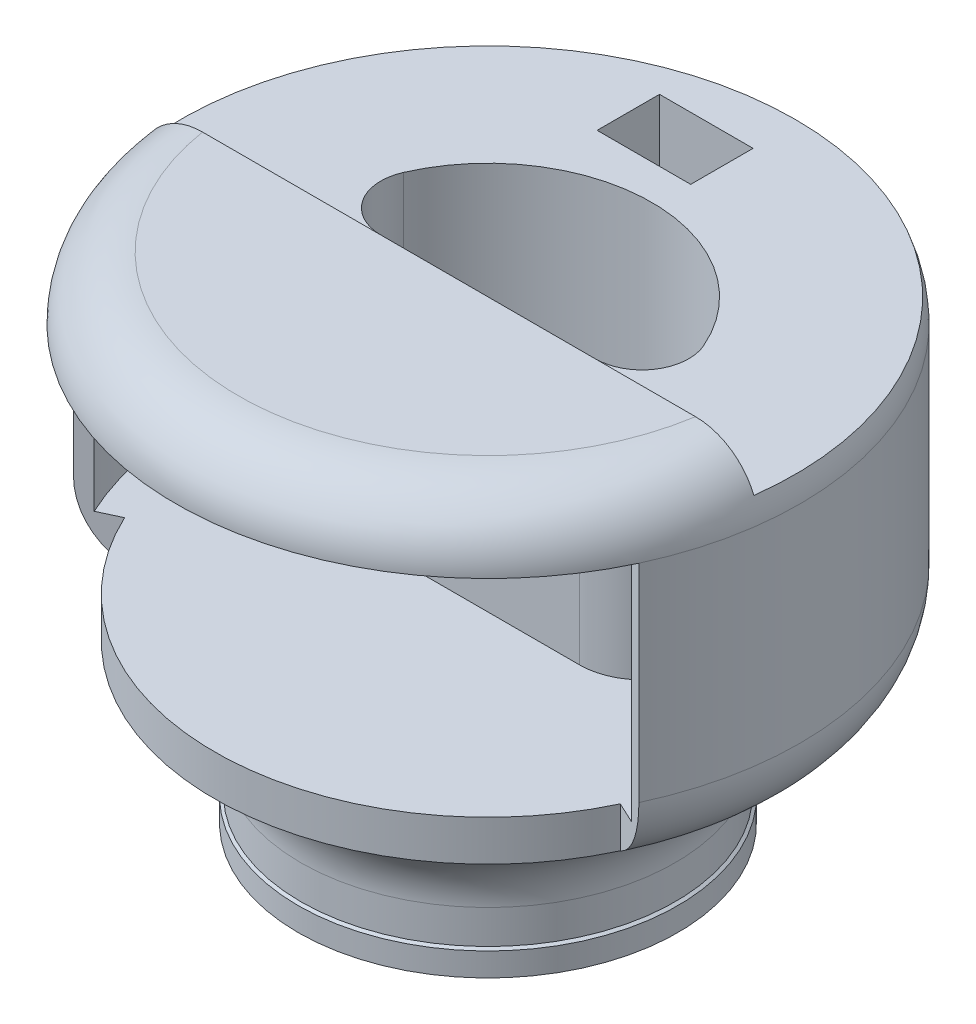
SolidWorks part; units mm, degrees
ref_plane "Front Plane" through (0, 0, 0) normal (0, 0, 1) x (1, 0, 0)
ref_plane "Top Plane" through (0, 0, 0) normal (0, 1, 0) x (1, 0, 0)
ref_plane "Right Plane" through (0, 0, 0) normal (1, 0, 0) x (0, 0, -1)
sketch "Sketch1" plane through (0, 0, 0) normal (0, 0, 1) x (1, 0, 0)
  line L0 (0, 0) -> (0, 90.2242) construction
  line L28 (0, 63.4279) -> (32, 63.4279)
  line L29 (40, 55.4279) -> (40, 28.8468)
  line L30 (22.5, 0) -> (24.35, 0)
  line L31 (24.35, 0) -> (24.35, 3)
  line L32 (24.35, 3) -> (24, 3.25)
  line L33 (24, 3.25) -> (24, 7.5811)
  line L34 (28.5399, 15.9588) -> (35.4601, 20.4691)
  line L35 (0, 13) -> (22, 13)
  line L36 (22.5, 12.5) -> (22.5, 0)
  line L37 (0, 13) -> (0, 63.4279)
  arc A0 (22, 13) -> (22.5, 12.5) centre (22, 12.5) cw
  arc A1 (24, 7.5811) -> (28.5399, 15.9588) centre (34, 7.5811) cw
  arc A2 (35.4601, 20.4691) -> (40, 28.8468) centre (30, 28.8468) ccw
  arc A3 (32, 63.4279) -> (40, 55.4279) centre (32, 55.4279) cw
  point P11 (22.9, 63.4279)
  point P18 (22.5, 13)
  point P21 (24, 13)
  point P24 (40, 23.4279)
  point P27 (40, 63.4279)
  point P28 (28.5604, 23.4279)
  point P31 (22.5, 17)
  dimension "D8" = 9.75
  dimension "D9" = 0.5
  dimension "D4" = 1.85
  dimension "D1" = 22.5
  dimension "D10" = 10
  dimension "D11" = 10
  dimension "D12" = 8
  dimension "D2" = 40
  dimension "D3" = 40
  dimension "D5" = 1.5
  dimension "D6" = 3
  dimension "D7" = 13
revolve "Revolve1" add sketch "Sketch1" angle 360 about L0
ref_plane "Plane1" through (0, 13, 0) normal (0, -1, 0) x (-1, 0, 0)
sketch "Sketch18" plane through (0, 0, 0) normal (0, 0, 1) x (1, 0, 0)
  line L0 (0, 0) -> (0, 101.5813) construction
  line L1 (-24.35, 0) -> (24.35, 0) construction
sketch "Sketch3" plane through (0, 0, 0) normal (0, 0, 1) x (1, 0, 0)
  point P0 (1.2404, 19.1989)
ref_point "Point1"
ref_plane "Plane2" through (0, 0, 22.9) normal (0, 0, 1) x (1, 0, 0)
ref_plane "Plane3" through (0, 0, 40) normal (0, 0, 1) x (1, 0, 0)
ref_plane "Plane4" through (0, 55.4279, 0) normal (0, 1, 0) x (1, 0, 0)
sketch "Sketch9" plane through (0, 55.4279, 0) normal (0, 1, 0) x (1, 0, 0)
  circle A7 centre (0, 0) radius 38
  circle A8 centre (0, 0) radius 40 construction
  circle A9 centre (0, 0) radius 23
  dimension "D1" = 2
  dimension "D2" = 46
ref_plane "Plane5" through (0, 13, 0) normal (0, -1, 0) x (-1, 0, 0)
sketch "Sketch11" plane through (0, 13, 0) normal (0, -1, 0) x (-1, 0, 0)
  line L0 (-21, 0) -> (21, 0)
  arc A1 (-21, 0) -> (21, 0) centre (0, 0) cw
  dimension "D1" = 42
extrude "Cut-Extrude3" cut sketch "Sketch11" against normal blind 60
ref_plane "Plane6" through (0, 0, -40) normal (0, 0, -1) x (-1, 0, 0)
extrude "Cut-Extrude5" cut sketch "Sketch9" against normal blind 30 and the other way blind 2
sketch "Sketch19" plane through (0, 0, 0) normal (1, 0, 0) x (0, 0, -1)
  line L0 (-47.0647, 55.4279) -> (-35.0647, 55.4279)
  line L1 (31.2976, 55.4279) -> (-31.2976, 55.4279) construction
  line L2 (-35.0647, 55.4279) -> (-35.0647, 18.9279)
  line L3 (-35.0647, 18.9279) -> (-47.0647, 18.9279)
  line L4 (-47.0647, 18.9279) -> (-47.0647, 55.4279)
  dimension "D1" = 12
  dimension "D2" = 36.5
revolve "Cut-Revolve2" cut sketch "Sketch19" angle 65 about L0 other way angle 65
ref_plane "Plane7" through (0, 0, 22.5) normal (0, 0, -1) x (-1, 0, 0)
sketch "Sketch21" plane through (0, 0, 22.5) normal (0, 0, -1) x (-1, 0, 0)
  line L0 (0, 0) -> (0, 101.5813) construction
  line L1 (-1.625, 4) -> (1.625, 4)
  line L2 (-1.625, 4) -> (-1.625, 0)
  line L3 (-1.625, 0) -> (1.625, 0)
  line L4 (1.625, 4) -> (1.625, 0)
  line L5 (-1.625, 4) -> (1.625, 0) construction
  line L6 (-1.625, 0) -> (1.625, 4) construction
  line L7 (-22.5, 0) -> (22.5, 0) construction
  point P0 (0, 2)
  dimension "D1" = 4
  dimension "D2" = 3.25
extrude "Boss-Extrude3" add sketch "Sketch21" along normal blind 1.35
pattern_circular "CirPattern1" count 5 over 360 about axis through (0, 0, 0) along (0, -1, 0) of "Boss-Extrude3"
ref_plane "Plane8" through (0, 20.4691, 0) normal (0, 1, 0) x (1, 0, 0)
sketch "Sketch22" plane through (0, 63.4279, 0) normal (0, 1, 0) x (1, 0, 0)
  line L0 (-40, 0) -> (40, 0)
  arc A0 (-40, 0) -> (40, 0) centre (0, 0) cw
  arc A1 (36.2523, -16.9047) -> (-36.2523, -16.9047) centre (0, 0) ccw construction
extrude "Cut-Extrude9" cut sketch "Sketch22" against normal blind 5
sketch "Sketch23" plane through (0, 0, -40) normal (0, 0, -1) x (-1, 0, 0)
  line L0 (0, 0) -> (0, 101.5813) construction
  line L1 (31.2976, 55.4279) -> (-31.2976, 55.4279) construction
  circle A0 centre (0, 42.1379) radius 10.5
  dimension "D1" = 21
  dimension "D2" = 13.29
extrude "Cut-Extrude10" cut sketch "Sketch23" against normal blind 10
sketch "Sketch24" plane through (0, 58.4279, 0) normal (0, 1, 0) x (1, 0, 0)
  line L1 (-14, 36) -> (3, 36)
  line L2 (-14, 36) -> (-14, 24)
  line L3 (-14, 24) -> (3, 24)
  line L4 (3, 36) -> (3, 24)
  line L5 (-14, 36) -> (3, 24) construction
  line L6 (-14, 24) -> (3, 36) construction
  point P0 (0, 30)
  point P8 (0, 0)
  point P9 (0, 0)
  dimension "D1" = 29
  dimension "D2" = 12
  dimension "D3" = 17
extrude "Boss-Extrude4" add sketch "Sketch24" against normal blind 8
sketch "Sketch26" plane through (0, 58.4279, 0) normal (0, 1, 0) x (1, 0, 0)
  line L0 (-14, 35.327) -> (-14, 24) construction
  line L1 (-11.5, 33.4915) -> (0.5, 33.4915)
  line L2 (-11.5, 33.4915) -> (-11.5, 25.4915)
  line L3 (-11.5, 25.4915) -> (0.5, 25.4915)
  line L4 (0.5, 33.4915) -> (0.5, 25.4915)
  line L5 (-11.5, 33.4915) -> (0.5, 25.4915) construction
  line L6 (-11.5, 25.4915) -> (0.5, 33.4915) construction
  arc A0 (39.4162, 0) -> (-39.4162, 0) centre (0, 0) ccw construction
  point P0 (-5.5, 29.4915)
  dimension "D1" = 30
  dimension "D2" = 8
  dimension "D3" = 12
  dimension "D4" = 2.5
extrude "Cut-Extrude11" cut sketch "Sketch26" against normal blind 10
sketch "Sketch27" plane through (3, 0, 0) normal (1, 0, 0) x (0, 0, -1)
  line L0 (36, 50.4279) -> (36, 57.4279) construction
  line L1 (27.5, 56.4279) -> (31.5, 56.4279)
  line L2 (27.5, 56.4279) -> (27.5, 51.4279)
  line L3 (27.5, 51.4279) -> (31.5, 51.4279)
  line L4 (31.5, 56.4279) -> (31.5, 51.4279)
  line L5 (27.5, 56.4279) -> (31.5, 51.4279) construction
  line L6 (27.5, 51.4279) -> (31.5, 56.4279) construction
  line L7 (24, 50.4279) -> (24, 57.4279) construction
  line L8 (24, 50.4279) -> (36, 50.4279) construction
  point P0 (29.5, 53.9279)
  dimension "D1" = 12
  dimension "D2" = 3.5
  dimension "D3" = 5
  dimension "D4" = 4
  dimension "D5" = 5.5
extrude "Cut-Extrude12" cut sketch "Sketch27" against normal blind 5
ref_plane "Plane10" through (0, 58.4279, 0) normal (0, 1, 0) x (1, 0, 0)
sketch "Sketch28" plane through (0, 55.4279, 0) normal (0, 1, 0) x (1, 0, 0)
  line L0 (-22.9129, -2) -> (22.9129, -2)
  arc A0 (-22.9129, -2) -> (22.9129, -2) centre (0, 0) ccw
  dimension "D1" = 46
  dimension "D2" = 2
extrude "Cut-Extrude14" cut sketch "Sketch28" against normal blind 30 and the other way blind 2
sketch "Sketch29" plane through (0, 0, 0) normal (0, 0, -1) x (-1, 0, 0)
  line L0 (0, 0) -> (0, 101.5813) construction
  line L1 (32, 63.4279) -> (-32, 63.4279) construction
  circle A0 centre (-30.4162, 60.9279) radius 1
  circle A1 centre (30.4162, 60.9279) radius 1
  circle A2 centre (0, 60.9279) radius 1
  dimension "D1" = 2
  dimension "D2" = 2
  dimension "D3" = 2
  dimension "D4" = 2.5
  dimension "D5" = 2.5
  dimension "D6" = 2.5
  dimension "D7" = 9
  dimension "D8" = 9
extrude "Cut-Extrude15" cut sketch "Sketch29" against normal blind 15
fillet "Fillet1" radius 6 2 edges at (-21, 35.7139, 0) (21, 35.7139, 0)
fillet "Fillet2" radius 8 2 edges at (22.9129, 41.4279, 2) (-22.9129, 41.4279, 2)
sketch "Sketch30" plane through (0, 63.4279, 0) normal (0, 1, 0) x (1, 0, 0)
  line L0 (-32, 0) -> (32, 0) construction
  line L1 (-49.3805, 0) -> (48.3231, 0)
  line L2 (-49.3805, 0) -> (-49.3805, -5)
  line L3 (-49.3805, -5) -> (48.3231, -5)
  line L4 (48.3231, 0) -> (48.3231, -5)
  dimension "D1" = 5
  dimension "D2" = 0
extrude "Cut-Extrude16" cut sketch "Sketch30" against normal blind 5
